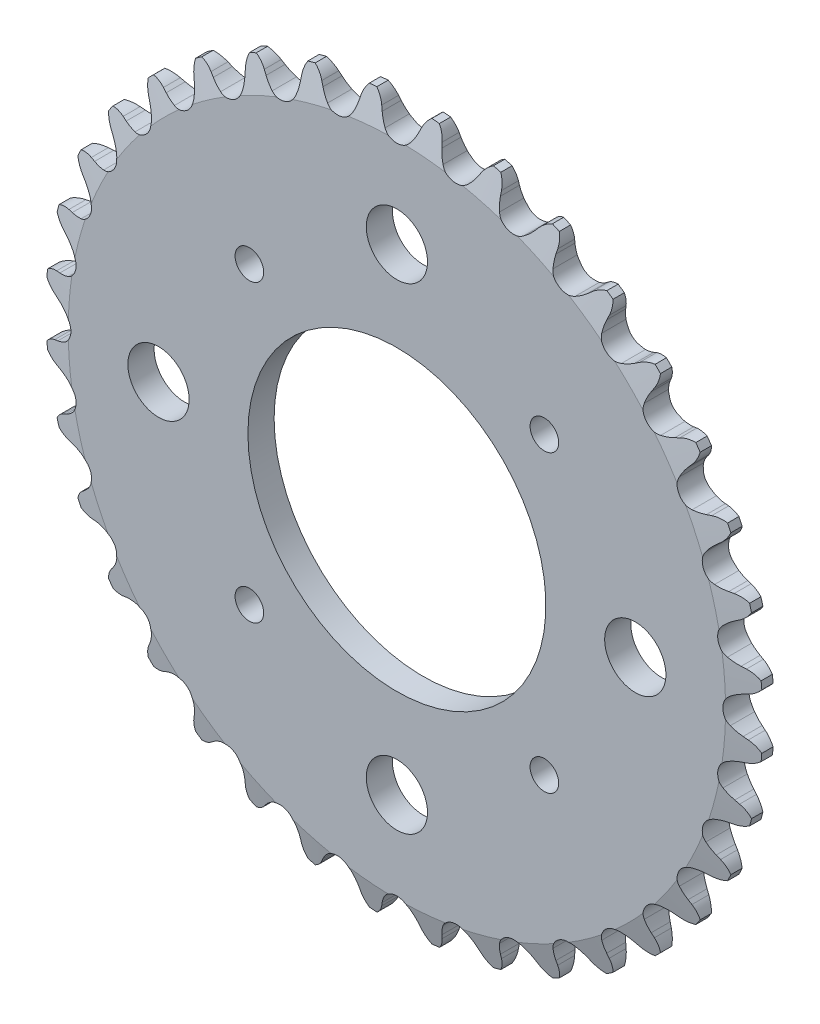
SolidWorks part; units mm, degrees
ref_plane "Front Plane" through (0, 0, 0) normal (0, 0, 1) x (1, 0, 0)
ref_plane "Top Plane" through (0, 0, 0) normal (0, 1, 0) x (1, 0, 0)
ref_plane "Right Plane" through (0, 0, 0) normal (1, 0, 0) x (0, 0, -1)
ref_axis "Axis1" through (0, 0, -88.99) along (0, 0, 1)
sketch "Sprocket-BaseSketch" plane through (0, 0, 0) normal (1, 0, 0) x (0, 0, -1)
  line L0 (1.397, 0) -> (1.397, 35.0204)
  line L1 (1.397, 35.0204) -> (0.6032, 38.1954)
  line L2 (0.6032, 38.1954) -> (-0.6032, 38.1954)
  line L3 (-0.6032, 38.1954) -> (-1.397, 35.0204)
  line L4 (-1.397, 35.0204) -> (-1.397, 0)
  line L5 (-1.397, 0) -> (1.397, 0)
  line L6 (5.588, 0) -> (-1.7463, 0) construction
  dimension "Hub Surface" = 1.397
  dimension "RightSide (1)" = 0.7938
  dimension "RightSide (2)" = 3.175
  dimension "OD" = 38.1954
  dimension "LeftSide (1)" = 0.7938
  dimension "LeftSide (2)" = 3.175
  dimension "Tooth Width" = 2.794
revolve "25 (04C) ANSI (ISO) Chain Number, 2.868in P.D." add sketch "Sprocket-BaseSketch" angle 360 about L6
sketch "Tooth-Sketch" plane through (0, 0, 0) normal (0, 0, 1) x (1, 0, 0)
  line L0 (0, 0) -> (0, 48.5721) construction
  line L1 (1.9526, 36.5067) -> (2.1137, 36.9439)
  line L2 (-1.9526, 36.5067) -> (-2.1137, 36.9439)
  line L3 (0, 36.429) -> (6.3258, 35.8756) construction
  line L4 (0, 36.429) -> (-6.3258, 35.8756) construction
  arc A0 (-1.3615, 35.4154) -> (1.3615, 35.4154) centre (0, 36.429) ccw
  arc A1 (1.3615, 35.4154) -> (1.9526, 36.5067) centre (-2.1189, 38.0065) ccw
  arc A2 (-1.3615, 35.4154) -> (-1.9526, 36.5067) centre (2.1189, 38.0065) cw
  arc A3 (2.1137, 36.9439) -> (4.6052, 38.6813) centre (4.6052, 36.0261) cw
  arc A4 (-2.1137, 36.9439) -> (-4.6052, 38.6813) centre (-4.6052, 36.0261) ccw
  arc A5 (4.6052, 38.6813) -> (-4.6052, 38.6813) centre (0, 0) ccw
extrude "Tooth-Cut, Number of teeth: 36" cut sketch "Tooth-Sketch" against normal through all and the other way through all
pattern_circular "Tooth Pattern, 36 / 36" count 36 every 10 about axis through (0, 0, -88.99) along (0, 0, 1) of "Tooth-Cut, Number of teeth: 36"
sketch "Sketch1" plane through (0, 0, -1.397) normal (0, 0, -1) x (-1, 0, 0)
  line L0 (-15.7154, 15.7154) -> (0, 0) construction
  line L1 (0, 0) -> (0, 25.4) construction
  circle A0 centre (0, 0) radius 15.875
  circle A1 centre (0, 25.4) radius 3.2639
  circle A2 centre (-15.7154, 15.7154) radius 1.524
  circle A3 centre (15.7154, 15.7154) radius 1.524
  circle A4 centre (25.4, 0) radius 3.2639
  circle A5 centre (15.7154, -15.7154) radius 1.524
  circle A6 centre (0, -25.4) radius 3.2639
  circle A7 centre (-15.7154, -15.7154) radius 1.524
  circle A8 centre (-25.4, 0) radius 3.2639
  dimension "D1" = 31.75
  dimension "D3" = 6.5278
  dimension "D4" = 3.048
  dimension "D7" = 4
  dimension "D2" = 45
  dimension "D5" = 22.225
  dimension "D6" = 25.4
extrude "Cut-Extrude1" cut sketch "Sketch1" against normal through all
